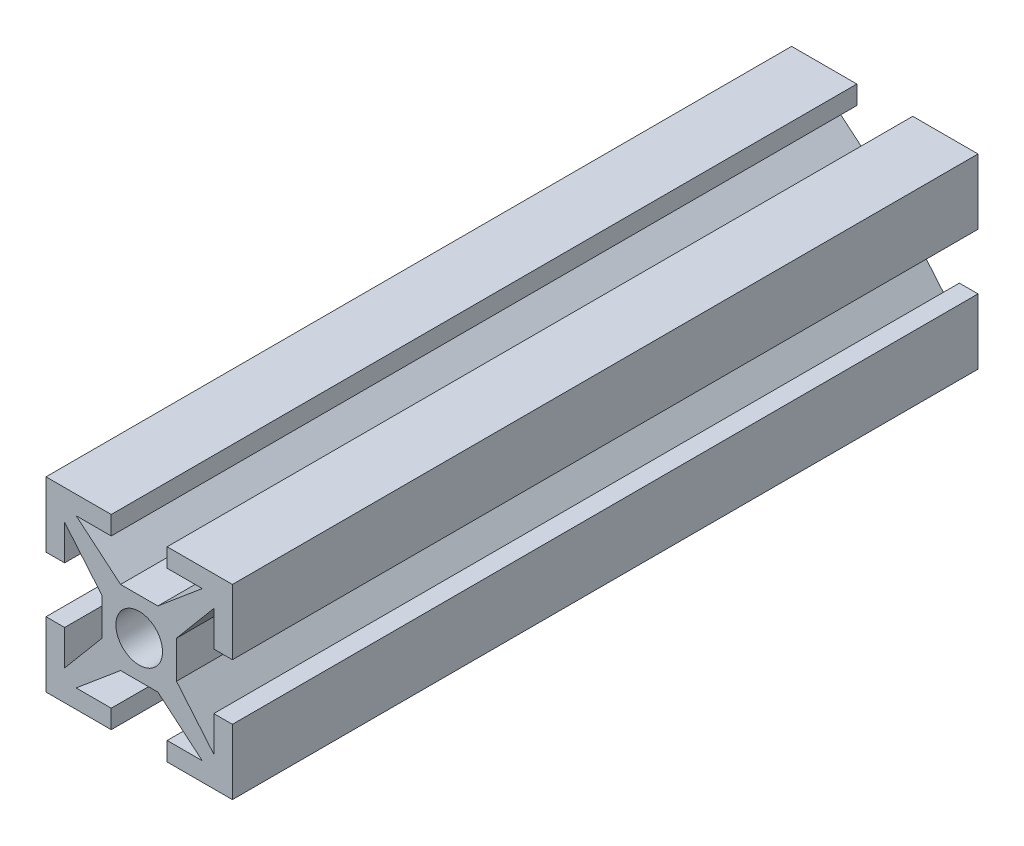
SolidWorks part; units mm, degrees
ref_plane "Front Plane" through (0, 0, 0) normal (0, 0, 1) x (1, 0, 0)
ref_plane "Top Plane" through (0, 0, 0) normal (0, 1, 0) x (1, 0, 0)
ref_plane "Right Plane" through (0, 0, 0) normal (1, 0, 0) x (0, 0, -1)
sketch "Esquisse2" plane through (0, 0, 0) normal (0, 0, 1) x (1, 0, 0)
  line L0 (-1, -2) -> (1, -2)
  line L1 (1, -2) -> (3.3835, -4)
  line L2 (3.3835, -4) -> (1.5, -4)
  line L3 (1.5, -4) -> (1.5, -5)
  line L4 (1.5, -5) -> (5, -5)
  line L5 (-1, -2) -> (-3.3835, -4)
  line L6 (-3.3835, -4) -> (-1.5, -4)
  line L7 (-1.5, -4) -> (-1.5, -5)
  line L8 (-1.5, -5) -> (-5, -5)
  line L9 (-5, -5) -> (-5, -1.5)
  line L10 (-5, -1.5) -> (-4, -1.5)
  line L11 (-4, -1.5) -> (-4, -3.3835)
  line L12 (-4, -3.3835) -> (-2, -1)
  line L13 (-2, -1) -> (-2, 1)
  line L14 (-2, 1) -> (-4, 3.3835)
  line L15 (-4, 3.3835) -> (-4, 1.5)
  line L16 (-4, 1.5) -> (-5, 1.5)
  line L17 (-5, 1.5) -> (-5, 5)
  line L18 (-5, 5) -> (-1.5, 5)
  line L19 (-1.5, 5) -> (-1.5, 4)
  line L20 (-1.5, 4) -> (-3.3835, 4)
  line L21 (-3.3835, 4) -> (-1, 2)
  line L22 (-1, 2) -> (1, 2)
  line L23 (1, 2) -> (3.3835, 4)
  line L24 (3.3835, 4) -> (1.5, 4)
  line L25 (1.5, 4) -> (1.5, 5)
  line L26 (1.5, 5) -> (5, 5)
  line L27 (5, 5) -> (5, 1.5)
  line L28 (5, 1.5) -> (4, 1.5)
  line L29 (4, 1.5) -> (4, 3.3835)
  line L30 (4, 3.3835) -> (2, 1)
  line L31 (2, -1) -> (2, 1)
  line L32 (2, -1) -> (4, -3.3835)
  line L33 (4, -3.3835) -> (4, -1.5)
  line L34 (4, -1.5) -> (5, -1.5)
  line L35 (5, -1.5) -> (5, -5)
  circle A0 centre (0, 0) radius 1.25
  point P4 (0, -2)
  point P34 (0, 2)
  point P40 (2, 0)
  dimension "D4" = 2.5
  dimension "D1" = 2
  dimension "D2" = 3.5
  dimension "D3" = 1
  dimension "D5" = 10
  dimension "D6" = 10
  dimension "D7" = 140
  dimension "D8" = 4
  dimension "D9" = 4
  dimension "D10" = 3.5
  dimension "D11" = 3
extrude "Main Extrusion" add sketch "Esquisse2" along normal blind 40
